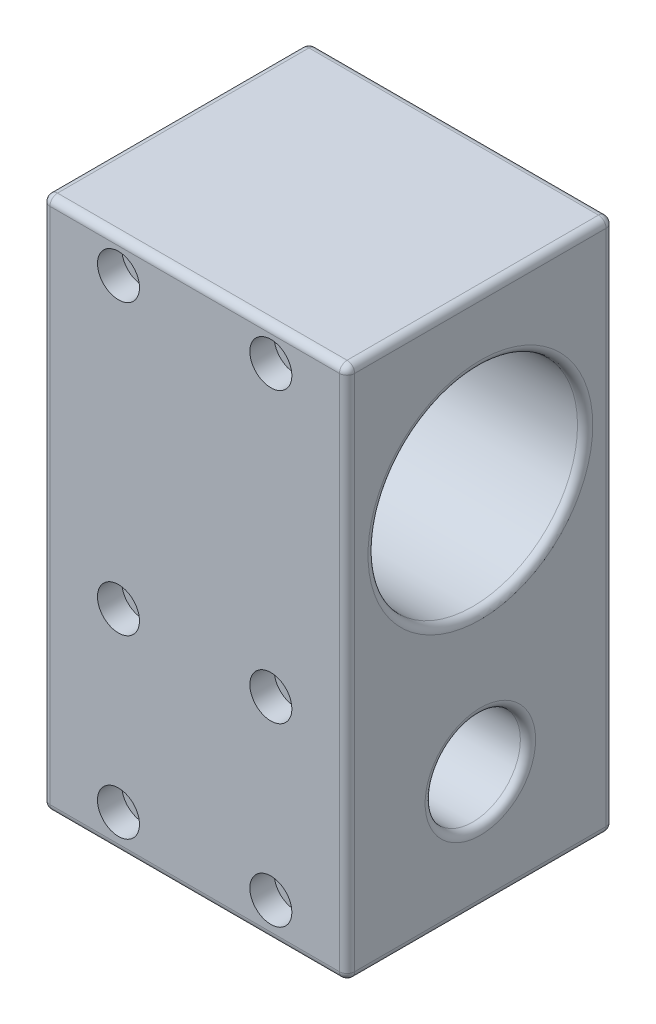
SolidWorks part; units mm, degrees
ref_plane "Front Plane" through (0, 0, 0) normal (0, 0, 1) x (1, 0, 0)
ref_plane "Top Plane" through (0, 0, 0) normal (0, 1, 0) x (1, 0, 0)
ref_plane "Right Plane" through (0, 0, 0) normal (1, 0, 0) x (0, 0, -1)
sketch "Sketch1" plane through (0, 0, 0) normal (1, 0, 0) x (0, 0, -1)
  line L1 (0, 0) -> (44.45, 0)
  line L2 (0, 0) -> (0, 88.9)
  line L3 (0, 88.9) -> (44.45, 88.9)
  line L4 (44.45, 0) -> (44.45, 88.9)
  circle A0 centre (22.225, 19.685) radius 7.9375
  circle A1 centre (22.225, 60.325) radius 17.4625
  point P11 (22.225, 88.9)
  dimension "D1" = 15.875
  dimension "D2" = 34.925
  dimension "D5" = 40.64
  dimension "D3" = 44.45
  dimension "D4" = 88.9
  dimension "D6" = 28.575
extrude "Boss-Extrude1" add sketch "Sketch1" along normal blind 50.8 contours A1 | A0 | L4 L3 L2 L1 region at (0, 19.685, -22.225) region at (0, 60.325, -22.225)
sketch "Sketch5" plane through (0, 0, 0) normal (0, 0, 1) x (1, 0, 0)
  circle A0 centre (38.1, 35.2425) radius 2.032
  circle A1 centre (38.1, 35.2425) radius 3.5
  circle A2 centre (12.7, 83.3438) radius 2.032
  circle A3 centre (12.7, 83.3438) radius 3.5
  circle A4 centre (38.1, 83.3438) radius 2.032
  circle A5 centre (38.1, 83.3438) radius 3.5
  circle A6 centre (12.7, 35.2425) radius 2.032
  circle A7 centre (12.7, 35.2425) radius 3.5
  circle A8 centre (38.1, 5.8737) radius 2.032
  circle A9 centre (38.1, 5.8737) radius 3.5
  circle A10 centre (12.7, 5.8737) radius 2.032
  circle A11 centre (12.7, 5.8737) radius 3.5
  point P24 (0, 0)
  point P25 (0, 0)
  point P26 (0, 0)
  point P27 (16.6702, 13.9063)
  point P28 (0, 0)
  point P29 (0, 0)
  point P30 (29.4374, 75.7582)
  point P31 (44.6024, 74.8233)
  point P32 (37.0078, 45.9143)
  point P33 (0, 0)
  point P34 (0, 0)
  point P35 (0, 0)
  point P36 (0, 0)
  point P37 (0, 0)
  point P38 (0, 0)
  dimension "D3" = 4.064
  dimension "D4" = 4.064
  dimension "D5" = 4.064
  dimension "D6" = 4.064
  dimension "D7" = 4.064
  dimension "D8" = 4.064
  dimension "D1" = 25.4
  dimension "D2" = 12.7
extrude "Cut-Extrude1" cut sketch "Sketch5" against normal through all contours A2 | A6 | A4 | A0 | A10 | A8 region at (12.7, 83.3438, 0) region at (12.7, 35.2425, 0)
extrude "Cut-Extrude2" cut sketch "Sketch5<3>" against normal blind 4.064 contours A3 | A5 | A1 | A7 | A11 | A9
sketch "Sketch5<3>" plane through (0, 0, 0) normal (0, 0, 1) x (1, 0, 0) same geometry as "Sketch5"
sketch "Sketch6" plane through (0, 0, -44.45) normal (0, 0, -1) x (-1, 0, 0)
  line L1 (-8.636, 83.3438) -> (-10.668, 86.8633)
  line L2 (-10.668, 86.8633) -> (-14.732, 86.8633)
  line L3 (-14.732, 86.8633) -> (-16.764, 83.3438)
  line L4 (-16.764, 83.3438) -> (-14.732, 79.8242)
  line L5 (-14.732, 79.8242) -> (-10.668, 79.8242)
  line L6 (-10.668, 79.8242) -> (-8.636, 83.3438)
  line L7 (-34.036, 83.3438) -> (-36.068, 86.8633)
  line L8 (-36.068, 86.8633) -> (-40.132, 86.8633)
  line L9 (-40.132, 86.8633) -> (-42.164, 83.3438)
  line L10 (-42.164, 83.3438) -> (-40.132, 79.8242)
  line L11 (-40.132, 79.8242) -> (-36.068, 79.8242)
  line L24 (-36.068, 79.8242) -> (-34.036, 83.3438)
  line L25 (-34.036, 35.2425) -> (-36.068, 38.762)
  line L26 (-36.068, 38.762) -> (-40.132, 38.762)
  line L39 (-40.132, 38.762) -> (-42.164, 35.2425)
  line L40 (-42.164, 35.2425) -> (-40.132, 31.723)
  line L41 (-40.132, 31.723) -> (-36.068, 31.723)
  line L54 (-36.068, 31.723) -> (-34.036, 35.2425)
  line L55 (-8.636, 35.2425) -> (-10.668, 38.762)
  line L56 (-10.668, 38.762) -> (-14.732, 38.762)
  line L69 (-14.732, 38.762) -> (-16.764, 35.2425)
  line L70 (-16.764, 35.2425) -> (-14.732, 31.723)
  line L71 (-14.732, 31.723) -> (-10.668, 31.723)
  line L84 (-10.668, 31.723) -> (-8.636, 35.2425)
  line L85 (-8.636, 5.8737) -> (-10.668, 9.3933)
  line L86 (-10.668, 9.3933) -> (-14.732, 9.3933)
  line L99 (-14.732, 9.3933) -> (-16.764, 5.8737)
  line L100 (-16.764, 5.8737) -> (-14.732, 2.3542)
  line L101 (-14.732, 2.3542) -> (-10.668, 2.3542)
  line L102 (-10.668, 2.3542) -> (-8.636, 5.8737)
  line L103 (-34.036, 5.8737) -> (-36.068, 9.3933)
  line L104 (-36.068, 9.3933) -> (-40.132, 9.3933)
  line L105 (-40.132, 9.3933) -> (-42.164, 5.8737)
  line L106 (-42.164, 5.8737) -> (-40.132, 2.3542)
  line L107 (-40.132, 2.3542) -> (-36.068, 2.3542)
  line L108 (-36.068, 2.3542) -> (-34.036, 5.8737)
  circle A7 centre (-12.7, 83.3438) radius 3.5195 construction
  circle A8 centre (-38.1, 83.3438) radius 3.5195 construction
  circle A9 centre (-38.1, 35.2425) radius 3.5195 construction
  circle A10 centre (-12.7, 35.2425) radius 3.5195 construction
  circle A11 centre (-12.7, 5.8737) radius 3.5195 construction
  circle A12 centre (-38.1, 5.8737) radius 3.5195 construction
  circle M1 centre (-12.7, 5.8737) radius 2.032
  circle M2 centre (-38.1, 35.2425) radius 2.032
  circle M3 centre (-38.1, 83.3438) radius 2.032
  circle M4 centre (-12.7, 35.2425) radius 2.032
  circle M5 centre (-38.1, 5.8737) radius 2.032
  dimension "D1" = 4.064
  dimension "D2" = 4.064
  dimension "D3" = 4.064
  dimension "D4" = 4.064
  dimension "D5" = 4.064
  dimension "D6" = 4.064
extrude "Cut-Extrude3" cut sketch "Sketch6" against normal blind 2.54 contours L11 L24 L7 L8 L9 L10 M3 | L41 L54 L25 L26 L39 L40 M2 | L71 L84 L55 L56 L69 L70 M4 | L107 L108 L103 L104 L105 L106 M5 | L101 L102 L85 L86 L99 L100 M1 | L1 L2 L3 L4 L5 L6 region at (35.1451, 81.6377, -44.45) region at (35.1451, 33.5365, -44.45) region at (9.7451, 33.5365, -44.45) region at (9.7451, 4.1677, -44.45) region at (35.1451, 4.1677, -44.45)
fillet "Fillet1" radius 1.27 16 edges at (25.4, 0, 0) (25.4, 0, -44.45) (0, 19.685, -30.1625) (0, 0, -22.225) (50.8, 19.685, -30.1625) (50.8, 0, -22.225) (50.8, 60.325, -39.6875) (50.8, 44.45, 0) (50.8, 44.45, -44.45) (0, 60.325, -39.6875) (0, 44.45, 0) (0, 44.45, -44.45) (25.4, 88.9, 0) (0, 88.9, -22.225) (50.8, 88.9, -22.225) (25.4, 88.9, -44.45)
ref_plane "Plane1" through (0, 0, -22.225) normal (0, 0, 1) x (1, 0, 0)
